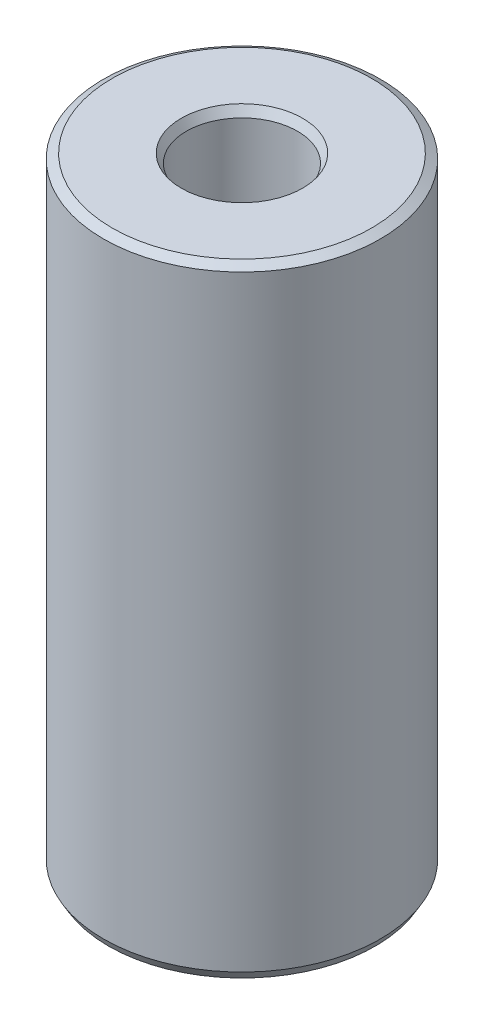
SolidWorks part; units mm, degrees
ref_plane "Front Plane" through (0, 0, 0) normal (0, 0, 1) x (1, 0, 0)
ref_plane "Top Plane" through (0, 0, 0) normal (0, 1, 0) x (1, 0, 0)
ref_plane "Right Plane" through (0, 0, 0) normal (1, 0, 0) x (0, 0, -1)
sketch "Sketch1" plane through (0, 0, 0) normal (0, 1, 0) x (1, 0, 0)
  circle A0 centre (0, 0) radius 10
  dimension "SLEEVE_OD" = 20
extrude "Boss-Extrude1" add sketch "Sketch1" along normal blind 44.7857
sketch "Sketch2" plane through (0, 0, 0) normal (0, 1, 0) x (1, 0, 0)
  circle A0 centre (0, 0) radius 4.0165
  dimension "BORE_D" = 8.0331
extrude "Cut-Extrude1" cut sketch "Sketch2" along normal through all
chamfer "Chamfer1" distance 0.3649 angle 60 4 edges at (0, 44.7857, 4.0165) (0, 0, 4.0165) (0, 0, 10) (0, 44.7857, 10) first distance on face at (0, 44.7857, 4.0165) first distance on face at (0, 0, 4.0165) first distance on face at (0, 44.7857, 10)
